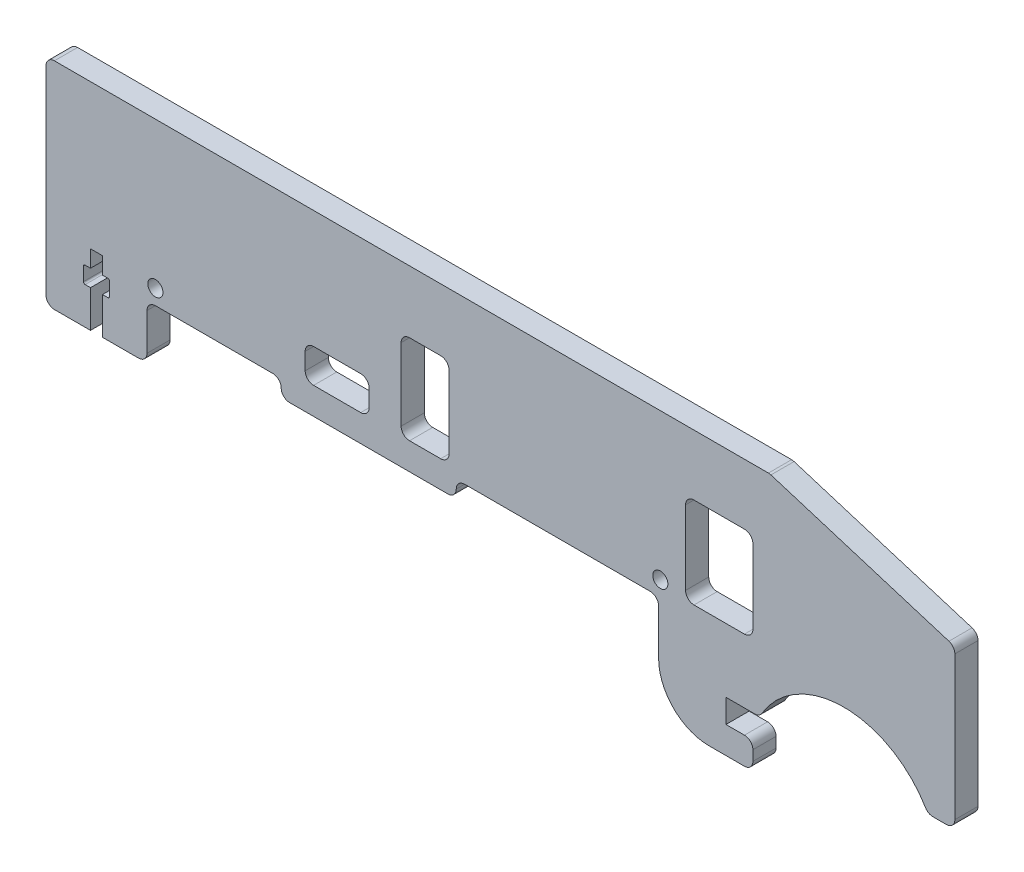
SolidWorks part; units mm, degrees
ref_plane "Front Plane" through (0, 0, 0) normal (0, 0, 1) x (1, 0, 0)
ref_plane "Top Plane" through (0, 0, 0) normal (0, 1, 0) x (1, 0, 0)
ref_plane "Right Plane" through (0, 0, 0) normal (1, 0, 0) x (0, 0, -1)
sketch "Sketch1" plane through (0, 0, 0) normal (0, 0, 1) x (1, 0, 0)
  line L1 (135, -32) -> (-135, -32)
  line L2 (135, -32) -> (135, 32)
  line L3 (135, 32) -> (-135, 32)
  line L4 (-135, -32) -> (-135, 32)
  line L5 (135, -32) -> (-135, 32) construction
  line L6 (135, 32) -> (-135, -32) construction
  point P0 (0, 0)
  dimension "D1" = 64
  dimension "D2" = 270
extrude "Boss-Extrude1" add sketch "Sketch1" along normal blind 6.88
sketch "Sketch2" plane through (0, 0, 6.88) normal (0, 0, 1) x (1, 0, 0)
  line L0 (-135, -32) -> (135, -32) construction
  line L1 (75, -13) -> (55, -13)
  line L2 (75, -13) -> (75, 14)
  line L3 (75, 14) -> (55, 14)
  line L4 (55, -13) -> (55, 14)
  line L5 (75, -13) -> (55, 14) construction
  line L6 (75, 14) -> (55, -13) construction
  line L7 (-135, 32) -> (-135, -32) construction
  line L9 (135, -32) -> (135, 32) construction
  line L11 (-135, -32) -> (135, -32) construction
  line L12 (-105, -32) -> (47, -32)
  line L13 (-105, -32) -> (-105, -16)
  line L14 (-105, -16) -> (47, -16)
  line L15 (47, -32) -> (47, -16)
  point P0 (65, 0.5)
  dimension "D1" = 16
  dimension "D2" = 30
  dimension "D3" = 152
  dimension "D4" = 20
  dimension "D5" = 27
  dimension "D6" = 46
  dimension "D7" = 60
extrude "Cut-Extrude1" cut sketch "Sketch2" against normal through all
sketch "Sketch3" plane through (0, 0, 6.88) normal (0, 0, 1) x (1, 0, 0)
  line L0 (-135, 32) -> (-135, -32) construction
  line L1 (-135, -32) -> (-105, -32) construction
  circle A2 centre (-102.5, -11.5) radius 2.25
  circle A3 centre (47.5, -11.5) radius 2.25
  dimension "D1" = 4.5
  dimension "D2" = 150
  dimension "D3" = 32.5
  dimension "D4" = 20.5
extrude "Cut-Extrude2" cut sketch "Sketch3" against normal through all
sketch "Sketch4" plane through (0, 0, 6.88) normal (0, 0, 1) x (1, 0, 0)
  line L0 (47, -32) -> (135, -32) construction
  line L1 (47, -32) -> (67, -32)
  line L2 (47, -32) -> (47, -47)
  line L3 (47, -47) -> (75, -47)
  line L4 (67, -32) -> (67, -39)
  line L5 (67, -39) -> (75, -39)
  line L6 (75, -39) -> (75, -47)
  line L7 (47, -32) -> (47, -16) construction
  dimension "D1" = 7
  dimension "D2" = 8
  dimension "D3" = 20
  dimension "D4" = 8
extrude "Boss-Extrude2" add sketch "Sketch4" against normal up to vertex (6.88 mm away) up to point (47, -16, 0)
sketch "Sketch5" plane through (0, 0, 6.88) normal (0, 0, 1) x (1, 0, 0)
  line L0 (-135, -32) -> (-105, -32) construction
  line L1 (-118.225, -53) -> (-121.775, -53)
  line L2 (-118.225, -53) -> (-118.225, -11)
  line L3 (-118.225, -11) -> (-121.775, -11)
  line L4 (-121.775, -53) -> (-121.775, -11)
  line L5 (-118.225, -53) -> (-121.775, -11) construction
  line L6 (-118.225, -11) -> (-121.775, -53) construction
  line L8 (-116.14, -21) -> (-123.86, -21)
  line L9 (-116.14, -21) -> (-116.14, -16)
  line L10 (-116.14, -16) -> (-123.86, -16)
  line L11 (-123.86, -21) -> (-123.86, -16)
  line L12 (-116.14, -21) -> (-123.86, -16) construction
  line L13 (-116.14, -16) -> (-123.86, -21) construction
  point P0 (-120, -32)
  point P7 (-120, -18.5)
  line M18 (-135, -32) -> (-105, -32)
  dimension "D1" = 3.55
  dimension "D2" = 21
  dimension "D3" = 11
  dimension "D4" = 7.72
  dimension "D5" = 5
extrude "Cut-Extrude3" cut sketch "Sketch5" against normal through all contours L9 L10 L2 L8 | L2 L10 L4 L8 | L10 L2 L3 L4 | L11 L8 L4 L10 | L2 L8 L4 M18 region at (-120, -26.5, 6.88) region at (-120, -18.5, 6.88) region at (-117.1825, -18.5, 6.88) region at (-122.8175, -18.5, 6.88) region at (-120, -13.5, 6.88)
sketch "Sketch7" plane through (0, 0, 0) normal (0, 0, -1) x (-1, 0, 0)
  line L0 (-55, -13) -> (-75, -13) construction
  line L1 (29.5, -13) -> (15.25, -13)
  line L2 (29.5, -13) -> (29.5, 13.5)
  line L3 (29.5, 13.5) -> (15.25, 13.5)
  line L4 (15.25, -13) -> (15.25, 13.5)
  line L5 (58, -13) -> (39, -13)
  line L6 (58, -13) -> (58, -3)
  line L7 (58, -3) -> (39, -3)
  line L8 (39, -13) -> (39, -3)
  line L9 (135, 32) -> (135, -32) construction
  dimension "D1" = 14.25
  dimension "D2" = 105.5
  dimension "D3" = 19
  dimension "D4" = 77
  dimension "D5" = 10
  dimension "D6" = 26.5
extrude "Cut-Extrude4" cut sketch "Sketch7" against normal through all
sketch "Sketch8" plane through (0, 0, 0) normal (0, 0, -1) x (-1, 0, 0)
  line L0 (39, -13) -> (58, -13) construction
  line L1 (-47, -16) -> (105, -16) construction
  line L2 (65.125, -21) -> (13.125, -21)
  line L3 (65.125, -21) -> (65.125, -13)
  line L4 (65.125, -13) -> (13.125, -13)
  line L5 (13.125, -21) -> (13.125, -13)
  line L6 (65.125, -21) -> (13.125, -13) construction
  line L7 (65.125, -13) -> (13.125, -21) construction
  point P4 (39.125, -17)
  dimension "D1" = 5
  dimension "D2" = 52
extrude "Boss-Extrude4" add sketch "Sketch8" against normal up to vertex (6.88 mm away) up to point (47, -16, 6.88)
sketch "Sketch9" plane through (0, 0, 0) normal (0, 0, -1) x (-1, 0, 0)
  line L0 (-67, -32) -> (-135, -32) construction
  line L1 (-135, -32) -> (-135, 32) construction
  line L2 (-102, -17) -> (-83.2281, -17) construction
  line L3 (-77, -32) -> (-127, -32)
  arc A0 (-77, -32) -> (-127, -32) centre (-102, -45.3333) ccw
  dimension "D1" = 8
  dimension "D2" = 50
  dimension "D3" = 15
extrude "Cut-Extrude5" cut sketch "Sketch9" against normal through all
fillet "Fillet2" radius 0.5 4 edges at (-116.14, -16, 3.44) (-116.14, -21, 3.44) (-123.86, -21, 3.44) (-123.86, -16, 3.44)
sketch "Sketch10" plane through (0, 0, 6.88) normal (0, 0, 1) x (1, 0, 0)
  line L0 (80, 32) -> (135, 15)
  line L1 (135, 32) -> (-135, 32) construction
  line L2 (135, -32) -> (135, 32) construction
  line L3 (80, 32) -> (135, 32)
  line L4 (135, 32) -> (135, 15)
  dimension "D1" = 55
  dimension "D2" = 17
extrude "Cut-Extrude6" cut sketch "Sketch10" against normal through all
fillet "Fillet1" radius 2.5 28 edges at (55, 14, 3.44) (75, 14, 3.44) (75, -13, 3.44) (55, -13, 3.44) (-135, 32, 3.44) (-135, -32, 3.44) (47, -16, 3.44) (-105, -16, 3.44) (-105, -32, 3.44) (75, -47, 3.44) (75, -39, 3.44) (135, -32, 3.44) (-58, -13, 3.44) (-39, -13, 3.44) (-39, -3, 3.44) (-58, -3, 3.44) (-29.5, 13.5, 3.44) (-15.25, 13.5, 3.44) (-15.25, -13, 3.44) (-29.5, -13, 3.44) (-65.125, -16, 3.44) (-65.125, -21, 3.44) (-13.125, -21, 3.44) (-13.125, -16, 3.44) (77, -32, 3.44) (127, -32, 3.44) (135, 15, 3.44) (80, 32, 3.44)
fillet "Fillet3" radius 15 1 edges at (47, -47, 3.44)
